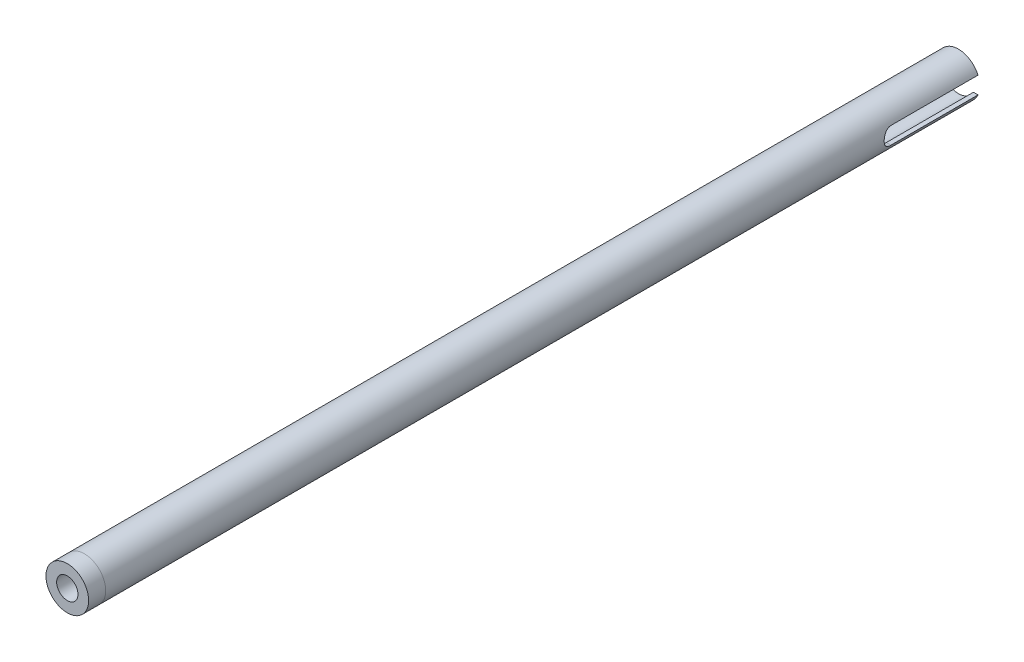
SolidWorks part; units mm, degrees
ref_plane "Front Plane" through (0, 0, 0) normal (0, 0, 1) x (1, 0, 0)
ref_plane "Top Plane" through (0, 0, 0) normal (0, 1, 0) x (1, 0, 0)
ref_plane "Right Plane" through (0, 0, 0) normal (1, 0, 0) x (0, 0, -1)
sketch "Axis" plane through (0, 0, 0) normal (0, 1, 0) x (1, 0, 0)
  line L0 (0, 0) -> (0, 331.464) construction
  line L1 (0, 0) -> (0, -28.575) construction
  line L2 (0, 331.464) -> (-7.9375, 331.464) construction
  line L4 (0, 360.8328) -> (-10.3188, 322.6534) construction
  dimension "D1" = 28.575
  dimension "D2" = 7.9375
sketch "Sketch1" plane through (0, 0, 0) normal (0, 0, 1) x (1, 0, 0)
  line L0 (-7.9375, 0) -> (7.9375, 0) construction
  line L1 (-7.2748, 3.175) -> (7.2748, 3.175)
  line L2 (-7.2748, -3.175) -> (7.2748, -3.175)
  circle A0 centre (0, 0) radius 7.9375
  circle A1 centre (0, 0) radius 6.4135
  circle A2 centre (0, 0) radius 3.9688
  dimension "D1" = 15.875
  dimension "D3" = 7.9375
  dimension "D2" = 1.524
  dimension "D4" = 6.35
extrude "Threaded insert 1-1" add sketch "Sketch1" against normal blind 6.35 contours A2 L1 A1 | A1 L1 A0 | A2 L0 A1 L1 | A1 L0 A0 L1 | L0 A1 L2 A0 | L0 A2 L2 A1 | A2 L2 A1 | A1 L2 A0 | L0 A1 L2 A2 | L0 A0 L2 A1 | A0 L0 A1 L1 | A1 L0 A2 L1 region at (4.7887, 1.6543, 0) region at (4.7887, -1.6543, 0) region at (6.9234, 1.6163, 0) region at (6.9234, -1.6163, 0) region at (-4.7887, -1.6543, 0) region at (-4.7887, 1.6543, 0) region at (0, 4.6159, 0) region at (0, -4.6159, 0) region at (0, 6.5666, 0) region at (6.4237, -3.3281, 0) region at (-6.9234, -1.6163, 0) region at (-6.9234, 1.6163, 0)
extrude "Threaded insert 1-2" add sketch "Sketch1<3>" against normal blind 9.525 from surface contours A2 L1 A1 | A2 L0 A1 L1 | L0 A2 L2 A1 | A2 L2 A1 | L0 A1 L2 A2 | A1 L0 A2 L1 region at (4.7887, 1.6543, 0) region at (4.7887, -1.6543, 0) region at (-4.7887, -1.6543, 0) region at (-4.7887, 1.6543, 0) region at (0, 4.6159, 0) region at (0, -4.6159, 0) starting at face at (7.9375, 0, -6.35)
sketch "Sketch1<3>" plane through (0, 0, 0) normal (0, 0, 1) x (1, 0, 0) same geometry as "Sketch1"
extrude "A-arm tube" add sketch "Sketch1<4>" against normal up to vertex (331.464 mm away) from surface separate body contours A1 L1 A0 | A1 L0 A0 L1 | L0 A1 L2 A0 | A1 L2 A0 | L0 A0 L2 A1 | A0 L0 A1 L1 region at (6.9234, 1.6163, 0) region at (6.9234, -1.6163, 0) region at (0, 6.5666, 0) region at (6.4237, -3.3281, 0) region at (-6.9234, -1.6163, 0) region at (-6.9234, 1.6163, 0) up to point (0, 0, -331.464) starting at face at (6.4135, 0, -6.35)
sketch "Sketch1<4>" plane through (0, 0, 0) normal (0, 0, 1) x (1, 0, 0) same geometry as "Sketch1"
extrude "Apex slot" cut sketch "Sketch1<5>" along normal blind 35.56 from surface contours A0 L0 A1 L1 | L0 A0 L2 A1 | A1 L0 A0 L1 | L0 A1 L2 A0 region at (6.9234, 1.6163, 0) region at (6.9234, -1.6163, 0) region at (-6.9234, -1.6163, 0) region at (-6.9234, 1.6163, 0) starting at face at (6.4135, 0, -331.464)
sketch "Sketch1<5>" plane through (0, 0, 0) normal (0, 0, 1) x (1, 0, 0) same geometry as "Sketch1"
fillet "Fillet1" radius 3.175 4 edges at (-6.4237, 3.175, -295.904) (-6.4237, -3.175, -295.904) (6.4237, -3.175, -295.904) (6.4237, 3.175, -295.904)
equation "\"tube diameter\"= 5 / 8"
equation "\"tube thickness\"= .06"
equation "\"apex thickness\"= .25"
equation "\"tube slot\"= 1.4"
equation "\"D1@Sketch1\"=\"tube diameter\""
equation "\"D2@Sketch1\"=\"tube thickness\""
equation "\"threaded insert hole\"= .3125"
equation "\"D3@Sketch1\"=\"threaded insert hole\""
equation "\"D4@Sketch1\"=\"apex thickness\""
equation "\"D1@Apex slot\" = \"tube slot\""
equation "\"D1@Fillet1\"=\"apex thickness\"/2"
equation "\"D2@Axis\"=\"tube diameter\"/2"
